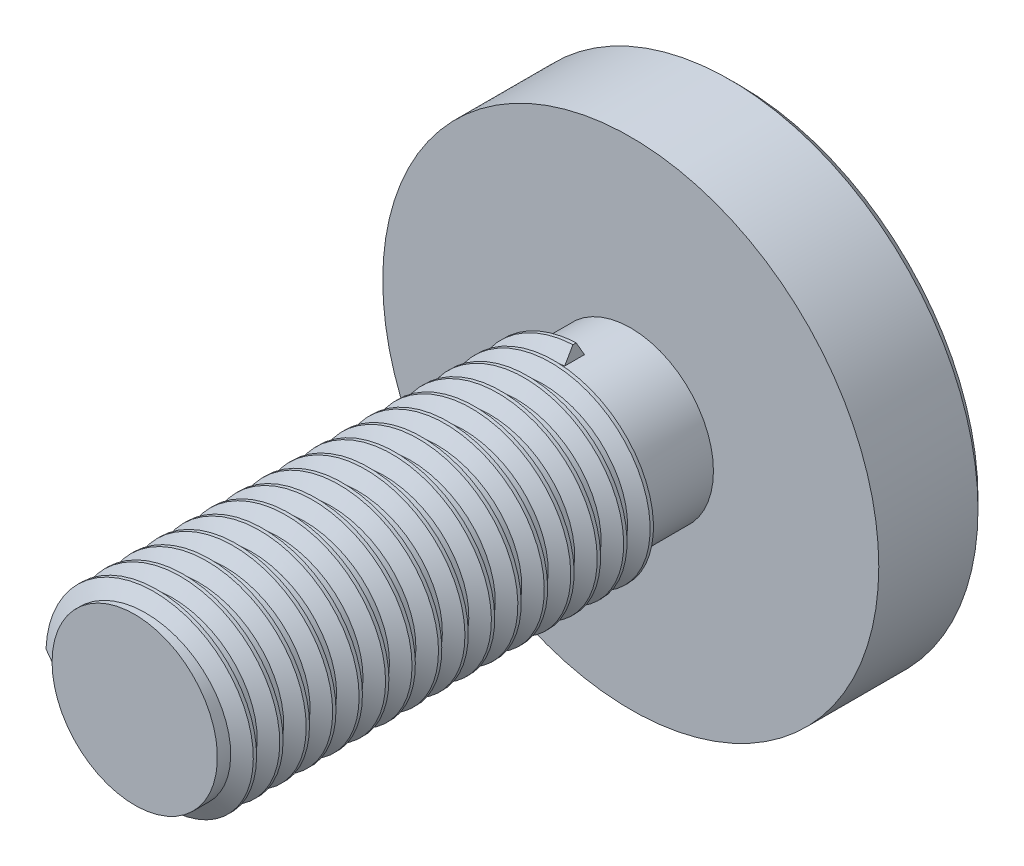
SolidWorks part; units mm, degrees
material "黄铜"
ref_plane "前视基准面" through (0, 0, 0) normal (0, 0, 1) x (1, 0, 0)
ref_plane "上视基准面" through (0, 0, 0) normal (0, 1, 0) x (1, 0, 0)
ref_plane "右视基准面" through (0, 0, 0) normal (1, 0, 0) x (0, 0, -1)
sketch "草图1" plane through (0, 0, 0) normal (0, 0, 1) x (1, 0, 0)
  circle A0 centre (0, 0) radius 7.5
extrude "凸台-拉伸1" add sketch "草图1" along normal blind 3.3
sketch "草图2" plane through (0, 0, 0) normal (0, 0, 1) x (1, 0, 0)
  circle A0 centre (0, 0) radius 2.5
extrude "凸台-拉伸2" add sketch "草图2" along normal blind 15 from surface starting at face at (7.5, 0, 3.3)
thread "螺纹线1" pitch 0.8 method extrude profile "螺纹线轮廓1" start angle 0, offset 0, length 13, pitch 0.8, diameter 5
ref_plane "基准面1" through (-2.5, 0, 18.3) normal (0, -1, 0) x (-1, 0, 0)
sketch "螺纹线轮廓1" plane through (-2.5, 0, 18.3) normal (0, -1, 0) x (-1, 0, 0)
  line L0 (0, 0) -> (0, 0.8) construction
  line L1 (0, 0) -> (0.433, 0.25)
  line L2 (0.433, 0.25) -> (0.433, 0.35)
  line L3 (0.433, 0.35) -> (0, 0.6)
  line L4 (0.433, 0.3) -> (0, 0.3) construction
  line L11 (0, 0) -> (0, 0.6)
  point P2 (0, 0)
  dimension "Pitch" = 0.8
  dimension "Profile_Angle" = 60
  dimension "Profile_Land" = 0.1
  dimension "Profile_Height" = 0.433
chamfer "倒角1" distance 0.3 angle 45 1 edges at (7.5, 0, 0)
